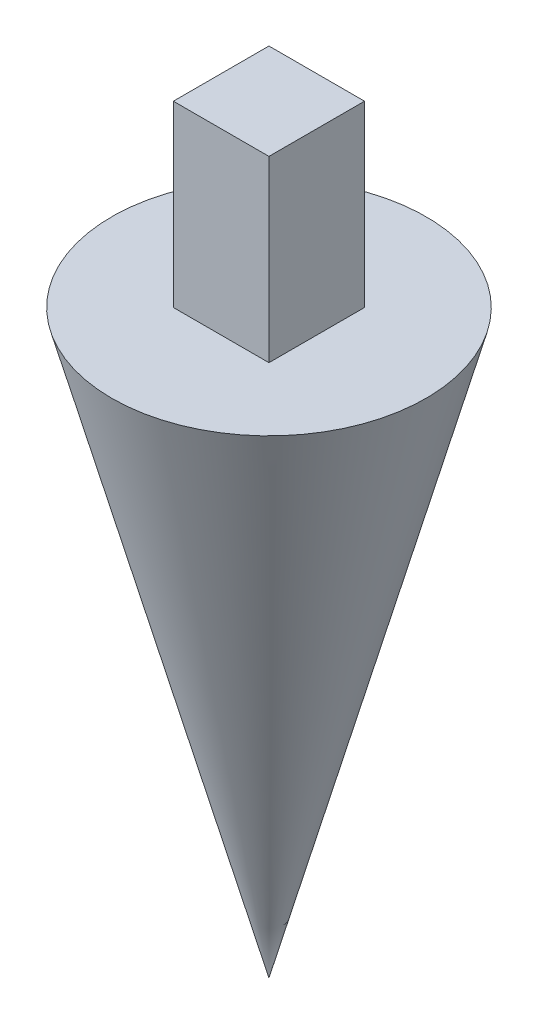
SolidWorks part; units mm, degrees
material "6061 Alloy"
ref_plane "Front Plane" through (0, 0, 0) normal (0, 0, 1) x (1, 0, 0)
ref_plane "Top Plane" through (0, 0, 0) normal (0, 1, 0) x (1, 0, 0)
ref_plane "Right Plane" through (0, 0, 0) normal (1, 0, 0) x (0, 0, -1)
sketch "Sketch1" plane through (0, 0, 0) normal (1, 0, 0) x (0, 0, -1)
  line L0 (0, 0) -> (0, -41.275)
  line L1 (0, -41.275) -> (11.176, 0)
  line L2 (11.176, 0) -> (0, 0)
  dimension "D1" = 41.275
  dimension "D2" = 11.176
revolve "Revolve1" add sketch "Sketch1" angle 360 about L0
sketch "Sketch2" plane through (0, 0, 0) normal (0, 1, 0) x (1, 0, 0)
  line L1 (-3.3973, 3.3973) -> (3.3972, 3.3973)
  line L2 (-3.3973, 3.3973) -> (-3.3973, -3.3972)
  line L3 (-3.3973, -3.3972) -> (3.3972, -3.3972)
  line L4 (3.3972, 3.3973) -> (3.3972, -3.3972)
  line L5 (-3.3973, 3.3973) -> (3.3972, -3.3972) construction
  line L6 (-3.3973, -3.3972) -> (3.3972, 3.3973) construction
  point P0 (0, 0)
  dimension "D1" = 6.7945
extrude "Boss-Extrude1" add sketch "Sketch2" along normal blind 12.7
equation "\"CONE-HEIGHT\" = 1 + 5 / 8"
equation "\"CONE-OD\"= 0.88"
equation "\"STUB-WIDTH\"= 0.2675"
equation "\"STUB-HEIGHT\"= 1 / 2"
equation "\"D1@Sketch1\"=\"CONE-HEIGHT\""
equation "\"D2@Sketch1\"=\"CONE-OD\"/2"
equation "\"D1@Sketch2\"=\"STUB-WIDTH\""
equation "\"D1@Boss-Extrude1\"=\"STUB-HEIGHT\""
